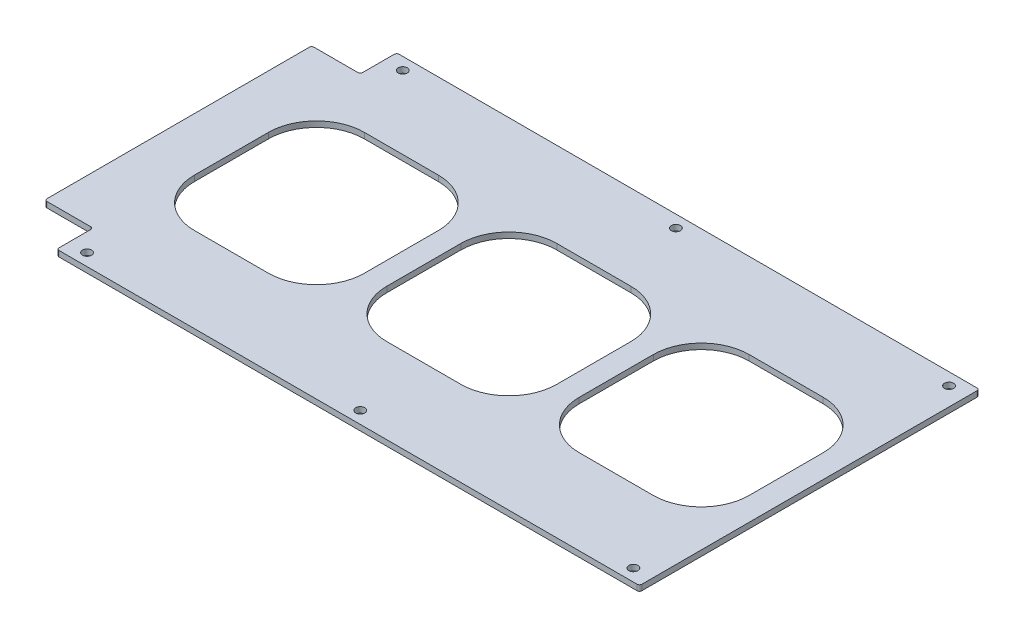
SolidWorks part; units mm, degrees
material "Acrylic (Medium-high impact)"
ref_plane "Front" through (0, 0, 0) normal (0, 0, 1) x (1, 0, 0)
ref_plane "Top" through (0, 0, 0) normal (0, 1, 0) x (1, 0, 0)
ref_plane "Right" through (0, 0, 0) normal (1, 0, 0) x (0, 0, -1)
sketch "Sketch1" plane through (0, 0, 0) normal (0, 1, 0) x (1, 0, 0)
  line L0 (-104.839, 25) -> (-104.839, -25) construction
  line L5 (-151.765, 88.9) -> (153.035, -88.9) construction
  line L6 (-151.765, -88.9) -> (151.765, 88.9) construction
  line L12 (-177.165, 69.85) -> (-151.765, -69.85) construction
  line L13 (-177.165, -69.85) -> (-151.765, 69.85) construction
  line L14 (-124.2065, 44.45) -> (-85.4715, 44.45)
  line L15 (-150.495, 88.9) -> (151.765, 88.9)
  line L20 (-149.289, 19.3675) -> (-149.289, -19.3675)
  line L21 (-124.2065, -44.45) -> (-85.4715, -44.45)
  line L26 (-60.389, 19.3675) -> (-60.389, -19.3675)
  line L27 (-149.289, 44.45) -> (-60.389, -44.45) construction
  line L32 (-149.289, -44.45) -> (-60.389, 44.45) construction
  line L33 (-23.5715, 44.45) -> (15.1635, 44.45)
  line L34 (153.035, 87.63) -> (153.035, -87.63)
  line L35 (151.765, -88.9) -> (-150.495, -88.9)
  line L36 (-151.765, -87.63) -> (-151.765, -71.12)
  line L37 (-153.035, -69.85) -> (-175.895, -69.85)
  line L38 (-177.165, -68.58) -> (-177.165, 68.58)
  line L39 (-175.895, 69.85) -> (-153.035, 69.85)
  line L40 (-151.765, 71.12) -> (-151.765, 87.63)
  line L41 (-48.654, 19.3675) -> (-48.654, -19.3675)
  line L42 (-23.5715, -44.45) -> (15.1635, -44.45)
  line L43 (40.246, 19.3675) -> (40.246, -19.3675)
  line L44 (-48.654, 44.45) -> (40.246, -44.45) construction
  line L45 (-48.654, -44.45) -> (40.246, 44.45) construction
  line L46 (77.0635, 44.45) -> (115.7985, 44.45)
  line L47 (51.981, 19.3675) -> (51.981, -19.3675)
  line L48 (77.0635, -44.45) -> (115.7985, -44.45)
  line L49 (140.881, 19.3675) -> (140.881, -19.3675)
  line L50 (51.981, 44.45) -> (140.881, -44.45) construction
  line L51 (51.981, -44.45) -> (140.881, 44.45) construction
  line L52 (-142.24, 82.55) -> (143.51, 82.55) construction
  line L53 (-142.24, 82.55) -> (-142.24, -82.55) construction
  line L54 (-142.24, -82.55) -> (143.51, -82.55) construction
  line L55 (143.51, 82.55) -> (143.51, -82.55) construction
  line L56 (96.431, 25) -> (96.431, -25) construction
  line L57 (-4.204, 25) -> (-4.204, -25) construction
  line L58 (-175.895, 69.85) -> (151.765, 69.85) construction
  line L59 (-177.165, -68.58) -> (-177.165, 68.58) construction
  arc A0 (51.981, -19.3675) -> (77.0635, -44.45) centre (77.0635, -19.3675) ccw
  arc A1 (115.7985, -44.45) -> (140.881, -19.3675) centre (115.7985, -19.3675) ccw
  arc A2 (115.7985, 44.45) -> (140.881, 19.3675) centre (115.7985, 19.3675) cw
  arc A15 (-175.895, -69.85) -> (-177.165, -68.58) centre (-175.895, -68.58) cw
  arc A16 (-151.765, -71.12) -> (-153.035, -69.85) centre (-153.035, -71.12) ccw
  arc A17 (-150.495, -88.9) -> (-151.765, -87.63) centre (-150.495, -87.63) cw
  arc A18 (153.035, -87.63) -> (151.765, -88.9) centre (151.765, -87.63) cw
  arc A19 (151.765, 88.9) -> (153.035, 87.63) centre (151.765, 87.63) cw
  arc A20 (-150.495, 88.9) -> (-151.765, 87.63) centre (-150.495, 87.63) ccw
  arc A21 (-177.165, 68.58) -> (-175.895, 69.85) centre (-175.895, 68.58) cw
  arc A22 (77.0635, 44.45) -> (51.981, 19.3675) centre (77.0635, 19.3675) ccw
  arc A23 (-48.654, -19.3675) -> (-23.5715, -44.45) centre (-23.5715, -19.3675) ccw
  arc A24 (15.1635, -44.45) -> (40.246, -19.3675) centre (15.1635, -19.3675) ccw
  arc A25 (15.1635, 44.45) -> (40.246, 19.3675) centre (15.1635, 19.3675) cw
  arc A26 (-23.5715, 44.45) -> (-48.654, 19.3675) centre (-23.5715, 19.3675) ccw
  arc A27 (-149.289, -19.3675) -> (-124.2065, -44.45) centre (-124.2065, -19.3675) ccw
  arc A28 (-85.4715, -44.45) -> (-60.389, -19.3675) centre (-85.4715, -19.3675) ccw
  arc A29 (-85.4715, 44.45) -> (-60.389, 19.3675) centre (-85.4715, 19.3675) cw
  arc A30 (-124.2065, 44.45) -> (-149.289, 19.3675) centre (-124.2065, 19.3675) ccw
  circle A31 centre (-142.24, 82.55) radius 2.3813
  arc A35 (-153.035, 69.85) -> (-151.765, 71.12) centre (-153.035, 71.12) ccw
  circle A36 centre (143.51, 82.55) radius 2.3813
  circle A37 centre (0.635, 82.55) radius 2.3812
  circle A38 centre (-142.24, -82.55) radius 2.3813
  circle A39 centre (0.635, -82.55) radius 2.3812
  circle A40 centre (143.51, -82.55) radius 2.3813
  arc A41 (-89.6896, 19.887) -> (-119.9884, 19.887) centre (-104.839, 0) ccw construction
  arc A42 (-119.9884, -19.887) -> (-89.6896, -19.887) centre (-104.839, 0) ccw construction
  arc A43 (111.5804, 19.887) -> (81.2816, 19.887) centre (96.431, 0) ccw construction
  arc A44 (81.2816, -19.887) -> (111.5804, -19.887) centre (96.431, 0) ccw construction
  arc A45 (10.9454, 19.887) -> (-19.3534, 19.887) centre (-4.204, 0) ccw construction
  arc A46 (-19.3534, -19.887) -> (10.9454, -19.887) centre (-4.204, 0) ccw construction
  point P0 (-104.839, 0)
  point P13 (-4.204, 0)
  point P18 (96.431, 0)
  dimension "D6" = 25.0825
  dimension "D7" = 1.27
  dimension "D8" = 1.27
  dimension "D13" = 4.7625
  dimension "D1" = 177.8
  dimension "D2" = 304.8
  dimension "D3" = 139.7
  dimension "D4" = 25.4
  dimension "D5" = 88.9
  dimension "D9" = 285.75
  dimension "D10" = 165.1
  dimension "D11" = 9.525
  dimension "D12" = 6.35
extrude "Boss-Extrude1" add sketch "Sketch1" along normal blind 2.9718
